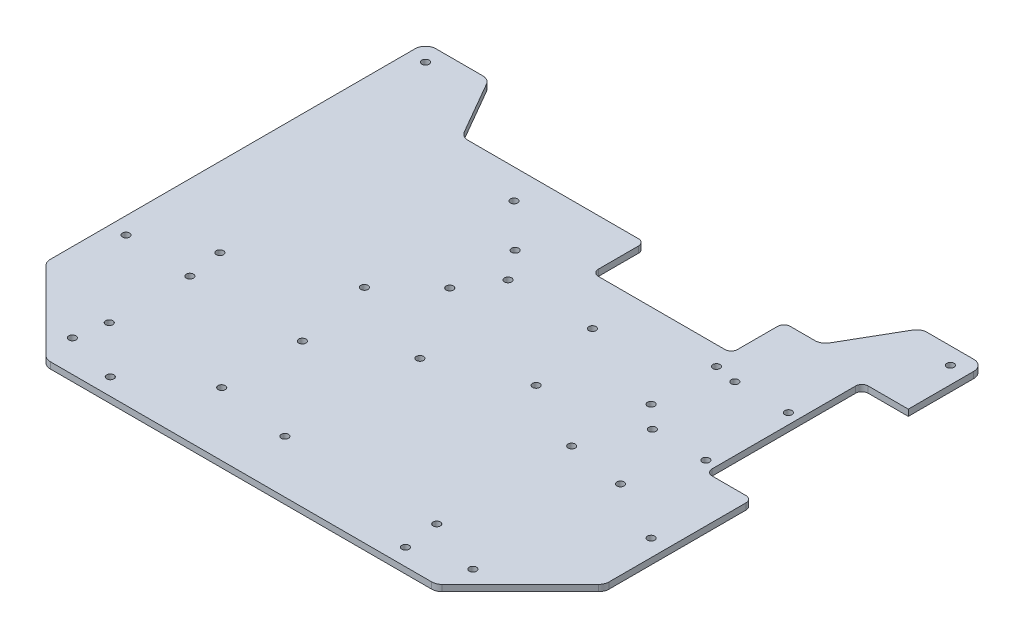
SolidWorks part; units mm, degrees
material "Acier non allié"
ref_plane "Front" through (0, 0, 0) normal (0, 0, 1) x (1, 0, 0)
ref_plane "Top" through (0, 0, 0) normal (0, 1, 0) x (1, 0, 0)
ref_plane "Right" through (0, 0, 0) normal (1, 0, 0) x (0, 0, -1)
sketch "Esquisse1" plane through (0, 0, 0) normal (0, 1, 0) x (1, 0, 0)
  line L0 (0, 0) -> (0, 190) construction
  line L1 (-92.5, 0) -> (92.5, 0)
  line L2 (92.5, 0) -> (132.5, 40)
  line L3 (132.5, 40) -> (132.5, 220)
  line L4 (132.5, 220) -> (102.5, 220)
  line L5 (102.5, 220) -> (85.1795, 190)
  line L6 (85.1795, 190) -> (-85.1795, 190)
  line L7 (-102.5, 220) -> (-85.1795, 190)
  line L8 (-132.5, 220) -> (-102.5, 220)
  line L9 (-132.5, 40) -> (-132.5, 220)
  line L10 (-92.5, 0) -> (-132.5, 40)
  dimension "D1" = 132.5
  dimension "D2" = 220
  dimension "D3" = 60
  dimension "D4" = 30
  dimension "D5" = 40
  dimension "D6" = 40
  dimension "D7" = 30
extrude "Boss.-Extru.1" add sketch "Esquisse1" along normal blind 3
fillet "Congé1" radius 5 10 edges at (92.5, 1.5, 0) (132.5, 1.5, -40) (132.5, 1.5, -220) (102.5, 1.5, -220) (85.1795, 1.5, -190) (-85.1795, 1.5, -190) (-102.5, 1.5, -220) (-132.5, 1.5, -220) (-92.5, 1.5, 0) (-132.5, 1.5, -40)
sketch "Esquisse2" plane through (0, 3, 0) normal (0, 1, 0) x (1, 0, 0)
  line L0 (0, 0) -> (0, 294.1173) construction
  line L2 (-90.4289, 0) -> (90.4289, 0) construction
  circle A0 centre (70, 8) radius 1
  circle A1 centre (124.5, 70) radius 1
  circle A2 centre (124.5, 212) radius 1
  circle A3 centre (-124.5, 212) radius 1
  circle A4 centre (-124.5, 70) radius 1
  circle A5 centre (-70, 8) radius 1
  dimension "D2" = 2
  dimension "D6" = 2
  dimension "D9" = 2
  dimension "D1" = 70
  dimension "D3" = 8
  dimension "D4" = 124.5
  dimension "D5" = 70
  dimension "D7" = 124.5
  dimension "D8" = 212
extrude "Enlèv. mat.-Extru.1" cut sketch "Esquisse2" against normal blind 3
hole_wizard "Dégagement M31" positions "Esquisse3" profile "Esquisse4" hole size "M3" standard "ISO" end condition through all
sketch "Esquisse3" plane through (0, 3, 0) normal (0, 1, 0) x (1, 0, 0)
  point P0 (70, 8)
  point P3 (-70, 8)
  point P6 (-124.5, 70)
  point P9 (-124.5, 212)
  point P12 (124.5, 212)
  point P15 (124.5, 70)
sketch "Esquisse4" plane through (70, 3, -8) normal (1, 0, 0) x (0, 0, 1)
  line L0 (0, 0) -> (0, 3)
  line L1 (0, 3) -> (1.7, 3)
  line L2 (1.7, 3) -> (1.7, 0)
  line L5 (1.7, 0) -> (0, 0)
  line L11 (0, -6.35) -> (0, 107.95) construction
  dimension "Diamètre du perçage jusqu'au prochain" = 3.4
  dimension "Profondeur du perçage jusqu'au prochain" = 3
sketch "Esquisse5" plane through (0, 3, 0) normal (0, 1, 0) x (1, 0, 0)
  line L0 (82.2927, 190) -> (-82.2927, 190) construction
  line L1 (67.5, 190) -> (1.5, 190)
  line L2 (67.5, 190) -> (67.5, 165)
  line L3 (67.5, 165) -> (1.5, 165)
  line L4 (1.5, 190) -> (1.5, 165)
  line L5 (132.5, 42.0711) -> (132.5, 215) construction
  line L6 (132.5, 184) -> (110.5, 184)
  line L7 (132.5, 184) -> (132.5, 110)
  line L8 (132.5, 110) -> (110.5, 110)
  line L9 (110.5, 184) -> (110.5, 110)
  line L10 (127.5, 220) -> (105.3868, 220) construction
  dimension "D1" = 25
  dimension "D2" = 65
  dimension "D3" = 131
  dimension "D4" = 36
  dimension "D5" = 110
  dimension "D6" = 22
extrude "Enlèv. mat.-Extru.2" cut sketch "Esquisse5" against normal through all
fillet "Congé2" radius 3 7 edges at (132.5, 1.5, -110) (110.5, 1.5, -110) (110.5, 1.5, -184) (67.5, 1.5, -190) (67.5, 1.5, -165) (1.5, 1.5, -165) (1.5, 1.5, -190)
sketch "Esquisse6" plane through (0, 3, 0) normal (0, 1, 0) x (1, 0, 0)
  line L0 (110.5, 140.5) -> (-167.6757, 140.5) construction
  line L1 (110.5, 181) -> (110.5, 113) construction
  line L2 (-90.4289, 0) -> (90.4289, 0) construction
  line L3 (110.5, 181) -> (110.5, 113) construction
  circle A0 centre (69.5, 156) radius 1
  circle A1 centre (-26, 156) radius 1
  circle A2 centre (-46.5, 176) radius 1
  circle A3 centre (69.5, 125) radius 1
  circle A4 centre (-26, 125) radius 1
  circle A5 centre (-46.5, 105) radius 1
  dimension "D4" = 2
  dimension "D6" = 2
  dimension "D10" = 2
  dimension "D1" = 140.5
  dimension "D2" = 41
  dimension "D3" = 15.5
  dimension "D5" = 136.5
  dimension "D7" = 15.5
  dimension "D8" = 35.5
  dimension "D9" = 157
extrude "Enlèv. mat.-Extru.3" cut sketch "Esquisse6" against normal through all
hole_wizard "Dégagement M32" positions "Esquisse7" profile "Esquisse8" hole size "M3" standard "ISO"
sketch "Esquisse7" plane through (0, 3, 0) normal (0, 1, 0) x (1, 0, 0)
  point P0 (-46.5, 105)
  point P3 (-26, 125)
  point P6 (-26, 156)
  point P9 (-46.5, 176)
  point P12 (69.5, 156)
  point P15 (69.5, 125)
sketch "Esquisse8" plane through (-46.5, 3, -105) normal (1, 0, 0) x (0, 0, 1)
  line L0 (0, 0) -> (0, 11.0215)
  line L1 (0, 11.0215) -> (1.7, 10)
  line L2 (1.7, 10) -> (1.7, 0)
  line L5 (1.7, 0) -> (0, 0)
  line L10 (0, 11.0215) -> (-1.7, 10) construction
  line L11 (0, -6.35) -> (0, 107.95) construction
  dimension "Diamètre du perçage" = 3.4
  dimension "Profondeur du perçage" = 10
  dimension "Angle de pointe" = 118
sketch "Esquisse9" plane through (0, 3, 0) normal (0, 1, 0) x (1, 0, 0)
  line L0 (132.5, 42.0711) -> (132.5, 107) construction
  line L1 (-90.4289, 0) -> (90.4289, 0) construction
  line L2 (-132.5, 215) -> (-132.5, 42.0711) construction
  line L3 (-39.16, 30) -> (-92.5, 30) construction
  line L4 (-39.16, 30) -> (-39.16, 68.24) construction
  line L5 (-39.16, 68.24) -> (-92.5, 68.24) construction
  line L6 (-92.5, 30) -> (-92.5, 68.24) construction
  line L7 (-4.16, 25) -> (-4.16, 89) construction
  line L8 (4.5, 165) -> (64.5, 165) construction
  line L9 (24.5, 142.1606) -> (-15.5, 142.1606) construction
  line L10 (110.5, 181) -> (110.5, 113) construction
  line L11 (113.5, 110) -> (129.5, 110) construction
  circle A0 centre (105.5, 115) radius 1
  circle A3 centre (105.5, 154.12) radius 1
  circle A6 centre (-92.5, 68.24) radius 1
  circle A7 centre (-39.16, 68.24) radius 1
  circle A8 centre (-39.16, 30) radius 1
  circle A9 centre (-92.5, 30) radius 1
  circle A10 centre (-4.16, 89) radius 1
  circle A11 centre (67.84, 89) radius 1
  circle A12 centre (-4.16, 25) radius 1
  circle A13 centre (67.84, 25) radius 1
  circle A14 centre (-15.5, 142.1606) radius 1
  circle A15 centre (24.5, 142.1606) radius 1
  circle A16 centre (34.5, 105.5) radius 1
  circle A17 centre (80.1, 115) radius 1
  circle A18 centre (80.1, 154.12) radius 1
  dimension "D2" = 2
  dimension "D4" = 2
  dimension "D17" = 2
  dimension "D18" = 2
  dimension "D19" = 2
  dimension "D20" = 2
  dimension "D21" = 2
  dimension "D22" = 2
  dimension "D23" = 2
  dimension "D24" = 2
  dimension "D32" = 2
  dimension "D33" = 2
  dimension "D34" = 2
  dimension "D11" = 2
  dimension "D12" = 2
  dimension "D5" = 27
  dimension "25" = 27
  dimension "D10" = 39.12
  dimension "D13" = 38.24
  dimension "D14" = 53.34
  dimension "D15" = 30
  dimension "D16" = 40
  dimension "D25" = 72
  dimension "D26" = 72
  dimension "D27" = 64
  dimension "D28" = 64
  dimension "D29" = 35
  dimension "D30" = 25
  dimension "D31" = 25
  dimension "D36" = 38
  dimension "D37" = 40
  dimension "D39" = 10
  dimension "D7" = 5
  dimension "D8" = 25.4
  dimension "D9" = 25.4
  dimension "D40" = 39.12
  dimension "D35" = 59.5
  dimension "D38" = 76
extrude "Enlèv. mat.-Extru.4" cut sketch "Esquisse9" against normal through all
hole_wizard "Dégagement M33" positions "Esquisse10" profile "Esquisse11" hole size "M3" standard "ISO"
sketch "Esquisse10" plane through (0, 3, 0) normal (0, 1, 0) x (1, 0, 0)
  point P3 (105.5, 115)
  point P9 (105.5, 154.12)
  point P14 (80.1, 154.12)
  point P17 (80.1, 115)
sketch "Esquisse11" plane through (105.5, 3, -115) normal (1, 0, 0) x (0, 0, 1)
  line L0 (0, 0) -> (0, 11.0215)
  line L1 (0, 11.0215) -> (1.7, 10)
  line L2 (1.7, 10) -> (1.7, 0)
  line L5 (1.7, 0) -> (0, 0)
  line L10 (0, 11.0215) -> (-1.7, 10) construction
  line L11 (0, -6.35) -> (0, 107.95) construction
  dimension "Diamètre du perçage" = 3.4
  dimension "Profondeur du perçage" = 10
  dimension "Angle de pointe" = 118
sketch "Esquisse12" plane through (0, 3, 0) normal (0, 1, 0) x (1, 0, 0)
  line L2 (-90.4289, 0) -> (90.4289, 0) construction
  line L3 (95, 15) -> (-95, 15) construction
  line L4 (95, 15) -> (95, 85) construction
  line L5 (95, 85) -> (-95, 85) construction
  line L6 (-95, 15) -> (-95, 85) construction
  line L7 (132.5, 42.0711) -> (132.5, 107) construction
  circle A4 centre (-95, 85) radius 1
  circle A5 centre (95, 85) radius 1
  circle A6 centre (95, 15) radius 1
  circle A7 centre (-95, 15) radius 1
  point P6 (95, 50)
  dimension "D5" = 2
  dimension "D6" = 2
  dimension "D7" = 2
  dimension "D8" = 2
  dimension "D1" = 70
  dimension "D2" = 190
  dimension "D3" = 15
  dimension "D4" = 37.5
extrude "Enlèv. mat.-Extru.5" cut sketch "Esquisse12" against normal through all and the other way through all
hole_wizard "Dégagement M34" positions "Esquisse13" profile "Esquisse14" hole size "M3" standard "ISO"
sketch "Esquisse13" plane through (0, 3, 0) normal (0, 1, 0) x (1, 0, 0)
  point P3 (-92.5, 68.24)
  point P6 (-92.5, 30)
  point P9 (-39.16, 30)
  point P12 (-39.16, 68.24)
  point P16 (-4.16, 25)
  point P19 (67.84, 25)
  point P22 (-4.16, 89)
  point P25 (67.84, 89)
  point P29 (34.5, 105.5)
  point P32 (24.5, 142.1606)
  point P35 (-15.5, 142.1606)
sketch "Esquisse14" plane through (-92.5, 3, -68.24) normal (1, 0, 0) x (0, 0, 1)
  line L0 (0, 0) -> (0, 11.0215)
  line L1 (0, 11.0215) -> (1.7, 10)
  line L2 (1.7, 10) -> (1.7, 0)
  line L5 (1.7, 0) -> (0, 0)
  line L10 (0, 11.0215) -> (-1.7, 10) construction
  line L11 (0, -6.35) -> (0, 107.95) construction
  dimension "Diamètre du perçage" = 3.4
  dimension "Profondeur du perçage" = 10
  dimension "Angle de pointe" = 118
hole_wizard "Dégagement M35" positions "Esquisse15" profile "Esquisse16" hole size "M3" standard "ISO"
sketch "Esquisse15" plane through (0, 3, 0) normal (0, 1, 0) x (1, 0, 0)
  point P0 (-95, 15)
  point P3 (-95, 85)
  point P6 (95, 85)
  point P9 (95, 15)
sketch "Esquisse16" plane through (-95, 3, -15) normal (1, 0, 0) x (0, 0, 1)
  line L0 (0, 0) -> (0, 11.0215)
  line L1 (0, 11.0215) -> (1.7, 10)
  line L2 (1.7, 10) -> (1.7, 0)
  line L5 (1.7, 0) -> (0, 0)
  line L10 (0, 11.0215) -> (-1.7, 10) construction
  line L11 (0, -6.35) -> (0, 107.95) construction
  dimension "Diamètre du perçage" = 3.4
  dimension "Profondeur du perçage" = 10
  dimension "Angle de pointe" = 118
equation "\"WIDTH\"= 300mm'Total width of the robot"
equation "\"LENGTH\"= 220mm'Total length of the robot"
equation "\"CUT_DEPTH\"= 45mm'Depth of the cut on the edges of the plate"
equation "\"Plate_th\"= 3mm'Thickness of the plate"
equation "\"D1\"= \"Plate_th\""
equation "\"D5@Esquisse9\"=\"25@Esquisse9\""
